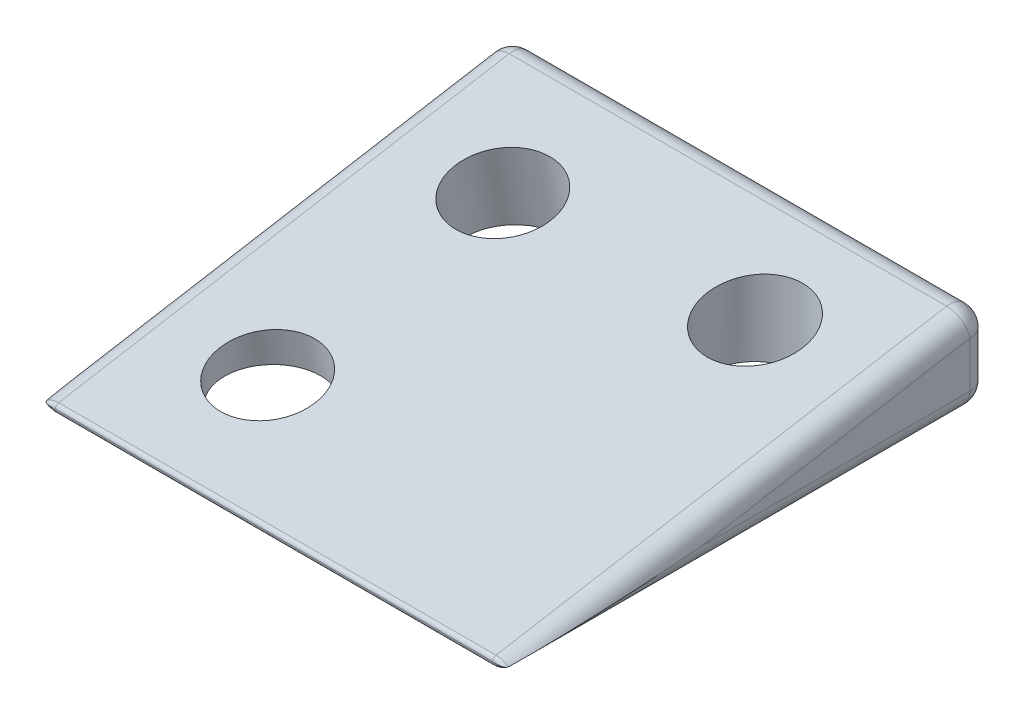
SolidWorks part; units mm, degrees
ref_plane "Front Plane" through (0, 0, 0) normal (0, 0, 1) x (1, 0, 0)
ref_plane "Top Plane" through (0, 0, 0) normal (0, 1, 0) x (1, 0, 0)
ref_plane "Right Plane" through (0, 0, 0) normal (1, 0, 0) x (0, 0, -1)
sketch "Sketch1" plane through (0, 0, 0) normal (0, 1, 0) x (1, 0, 0)
  line L1 (-9.525, -9.525) -> (9.525, -9.525)
  line L2 (-9.525, -9.525) -> (-9.525, 9.525)
  line L3 (-9.525, 9.525) -> (9.525, 9.525)
  line L4 (9.525, -9.525) -> (9.525, 9.525)
  line L5 (-9.525, -9.525) -> (9.525, 9.525) construction
  line L6 (-9.525, 9.525) -> (9.525, -9.525) construction
  point P0 (0, 0)
  dimension "D1" = 19.05
  dimension "D2" = 19.05
extrude "Boss-Extrude1" add sketch "Sketch1" along normal blind 6.35
sketch "Sketch4" plane through (-9.525, 0, 0) normal (-1, 0, 0) x (0, 0, 1)
  line L1 (9.525, 6.35) -> (9.525, 0) construction
  line L2 (-59.4387, 12.0907) -> (46.9704, -6.0836) construction
  line L3 (9.525, 0.3119) -> (-9.525, 3.5656)
  line L4 (-9.525, 6.35) -> (-9.525, 0) construction
  line L7 (9.525, 0.3119) -> (9.525, 6.35)
  line L8 (9.525, 6.35) -> (-9.525, 6.35)
  line L9 (-9.525, 6.35) -> (-9.525, 3.5656)
extrude "Cut-Extrude4" cut sketch "Sketch4" against normal through all both and the other way through all
sketch "Sketch5" plane through (0, 1.9111, 0.162) normal (0, -0.9857, -0.1684) x (1, 0, 0)
  line L0 (-9.525, -9.227) -> (-9.525, 9.5511) construction
  line L1 (-4.7625, 4.9245) -> (-4.7625, -4.6005) construction
  circle A0 centre (-4.7625, -4.6005) radius 1.905
  circle A1 centre (-4.7625, 4.9245) radius 1.905
  point P2 (-4.7625, 0.162)
  dimension "D2" = 3.81
  dimension "D1" = 4.7625
  dimension "D3" = 9.525
extrude "Cut-Extrude5" cut sketch "Sketch5" against normal through all both and the other way through all
sketch "Sketch7" plane through (0, 0, 0) normal (0, -1, 0) x (1, 0, 0)
  line L0 (9.525, 9.525) -> (9.525, -9.525) construction
  circle A0 centre (4.7625, -4.9163) radius 1.905
  dimension "D2" = 3.81
  dimension "D1" = 4.7625
extrude "Cut-Extrude6" cut sketch "Sketch7" against normal through all both and the other way through all
fillet "Fillet2" radius 0.7937 8 edges at (9.525, 0, 0) (9.525, 1.9388, 0) (0, 0, -9.525) (9.525, 1.7828, -9.525) (0, 3.5656, -9.525) (-9.525, 0, 0) (-9.525, 1.7828, -9.525) (-9.525, 1.9388, 0)
fillet "Fillet3" radius 0.1588 6 edges at (-8.9791, 0.0397, 9.525) (8.9791, 0.0397, 9.525) (8.9791, 0.2716, 9.525) (-8.9791, 0.2716, 9.525) (0, 0, 9.525) (0, 0.3119, 9.525)
